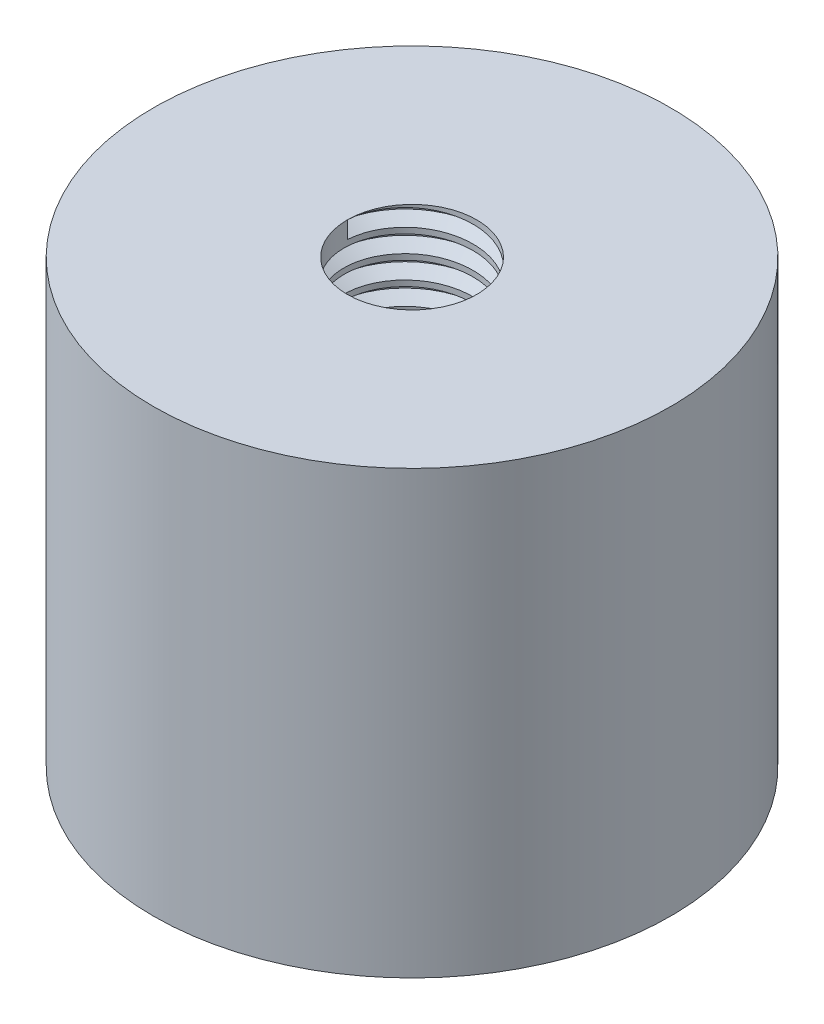
SolidWorks part; units mm, degrees
ref_plane "Front Plane" through (0, 0, 0) normal (0, 0, 1) x (1, 0, 0)
ref_plane "Top Plane" through (0, 0, 0) normal (0, 1, 0) x (1, 0, 0)
ref_plane "Right Plane" through (0, 0, 0) normal (1, 0, 0) x (0, 0, -1)
sketch "Sketch1" plane through (0, 0, 0) normal (0, 1, 0) x (1, 0, 0)
  circle A0 centre (0, 0) radius 17
  dimension "D1" = 34
extrude "Boss-Extrude1" add sketch "Sketch1" against normal blind 29 contours A0
sketch "Sketch2" plane through (0, 0, 0) normal (0, 1, 0) x (1, 0, 0)
  point P0 (0, 0)
hole_wizard "Tap Drill for M10x1.5 Tap1" positions "Sketch2" profile "Sketch3" hole size "M10x1.5" standard "ANSI Metric" end condition through all
sketch "Sketch3" plane through (0, 0, 0) normal (1, 0, 0) x (0, 0, 1)
  line L0 (0, 0) -> (0, 29)
  line L1 (0, 29) -> (4.25, 29)
  line L2 (4.25, 29) -> (4.25, 0)
  line L5 (4.25, 0) -> (0, 0)
  line L11 (0, -6.35) -> (0, 107.95) construction
  dimension "Thru Hole Dia." = 8.5
  dimension "Thru Hole Depth" = 29
thread "Thread1" pitch 1.5 method cut profile "Thread Profile1" start angle 0, offset 0, length 0, pitch 1.5, diameter 8.5
ref_plane "Plane1" through (-4.25, 0, 0) normal (0, 0, 1) x (-1, 0, 0)
sketch "Thread Profile1" plane through (-4.25, 0, 0) normal (0, 0, 1) x (-1, 0, 0)
  line L0 (0, 0) -> (0, 1.5) construction
  line L1 (0, 0) -> (0.8119, 0.4687)
  line L2 (0.8119, 0.4687) -> (0.8119, 0.6562)
  line L3 (0.8119, 0.6562) -> (0, 1.125)
  line L4 (0.8119, 0.5625) -> (0, 0.5625) construction
  line L11 (0, 0) -> (0, 1.125)
  point P2 (0, 0)
  dimension "Pitch" = 1.5
  dimension "Profile_Angle" = 60
  dimension "Profile_Land" = 0.1875
  dimension "Profile_Height" = 0.8119
